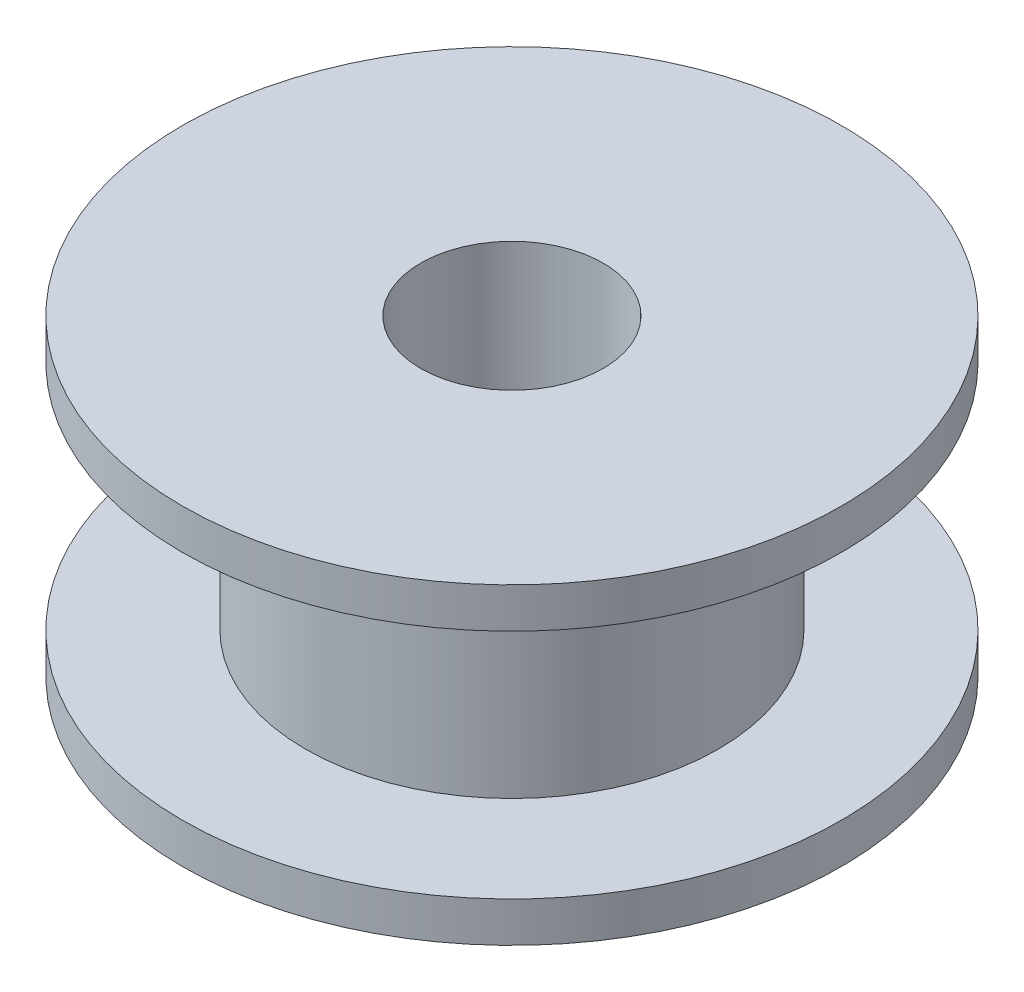
SolidWorks part; units mm, degrees
ref_plane "Front" through (0, 0, 0) normal (0, 0, 1) x (1, 0, 0)
ref_plane "Top" through (0, 0, 0) normal (0, 1, 0) x (1, 0, 0)
ref_plane "Right" through (0, 0, 0) normal (1, 0, 0) x (0, 0, -1)
sketch "Sketch1" plane through (0, 0, 0) normal (0, 1, 0) x (1, 0, 0)
  circle A0 centre (0, 0) radius 9.025
  circle A1 centre (0, 0) radius 5.655
  dimension "D1" = 11.31
  dimension "D2" = 18.05
extrude "Boss-Extrude1" add sketch "Sketch1" along normal blind 6.35 contours A1 region at (0, 0, 0)
extrude "Boss-Extrude2" add sketch "Sketch1<3>" against normal blind 1.1 contours A1 | A0 A1 region at (-8.7697, 0, 0) region at (0, 0, 0)
sketch "Sketch1<3>" plane through (0, 0, 0) normal (0, 1, 0) x (1, 0, 0) same geometry as "Sketch1"
extrude "Boss-Extrude3" add sketch "Sketch1<4>" along normal blind 1.1 from offset 6.35 contours A1 | A0 A1 region at (-8.7697, 0, 0) region at (0, 0, 0)
sketch "Sketch1<4>" plane through (0, 0, 0) normal (0, 1, 0) x (1, 0, 0) same geometry as "Sketch1"
sketch "Sketch2" plane through (0, 7.45, 0) normal (0, 1, 0) x (1, 0, 0)
  circle A0 centre (0, 0) radius 2.5
  dimension "D1" = 5
extrude "Cut-Extrude1" cut sketch "Sketch2" against normal up to next
